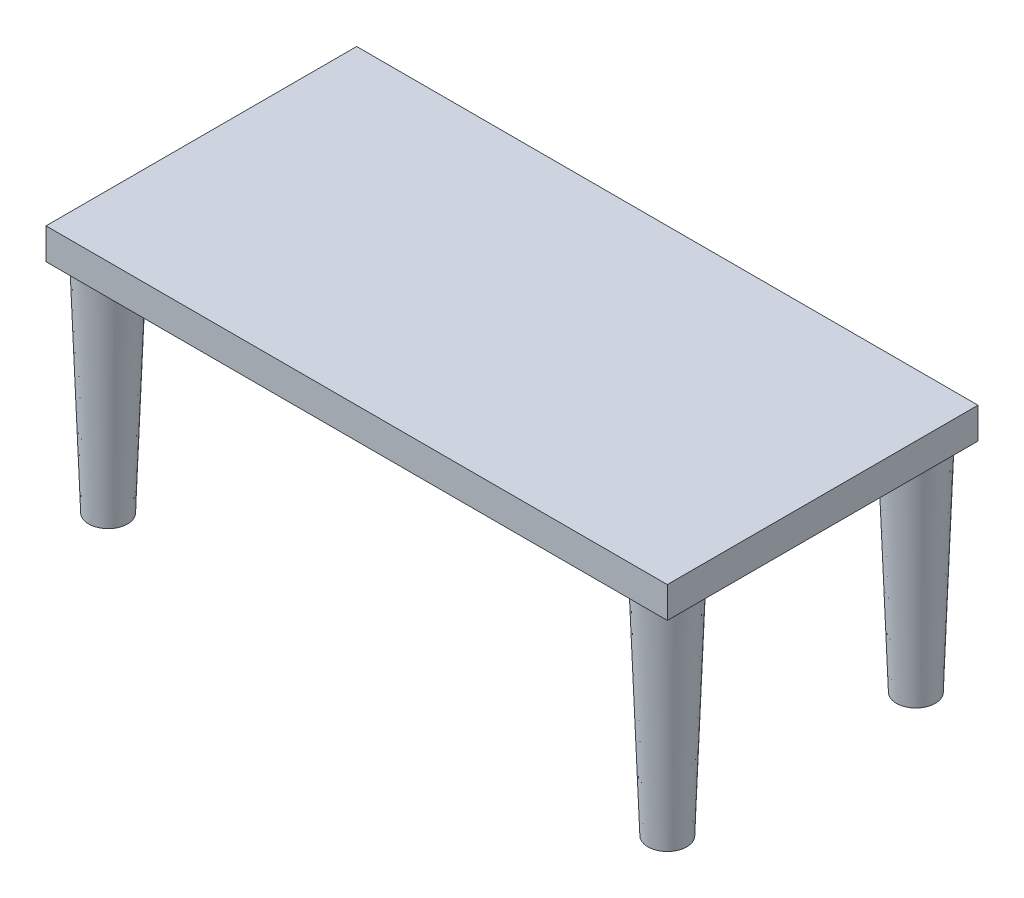
SolidWorks part; units mm, degrees
ref_plane "Front Plane" through (0, 0, 0) normal (0, 0, 1) x (1, 0, 0)
ref_plane "Top Plane" through (0, 0, 0) normal (0, 1, 0) x (1, 0, 0)
ref_plane "Right Plane" through (0, 0, 0) normal (1, 0, 0) x (0, 0, -1)
sketch "Sketch1" plane through (0, 0, 0) normal (0, 1, 0) x (1, 0, 0)
  line L1 (-100, 50) -> (100, 50)
  line L2 (-100, 50) -> (-100, -50)
  line L3 (-100, -50) -> (100, -50)
  line L4 (100, 50) -> (100, -50)
  line L5 (-100, 50) -> (100, -50) construction
  line L6 (-100, -50) -> (100, 50) construction
  point P0 (0, 0)
  dimension "D1" = 100
  dimension "D2" = 200
extrude "Boss-Extrude1" add sketch "Sketch1" along normal mid plane 10
ref_plane "Plane1" through (0, -75, 0) normal (0, 1, 0) x (1, 0, 0)
sketch "Sketch2" plane through (0, -5, 0) normal (0, -1, 0) x (1, 0, 0)
  line L0 (-100, -50) -> (-100, 50) construction
  line L1 (100, -50) -> (-100, -50) construction
  line L2 (100, 50) -> (100, -50) construction
  line L3 (-100, 50) -> (100, 50) construction
  circle A0 centre (-90, 40) radius 8.75
  circle A1 centre (90, 40) radius 8.75
  circle A2 centre (90, -40) radius 8.75
  circle A3 centre (-90, -40) radius 8.75
  dimension "D1" = 17.5
  dimension "D2" = 10
  dimension "D3" = 10
  dimension "D4" = 10
  dimension "D5" = 10
  dimension "D6" = 10
  dimension "D7" = 10
  dimension "D8" = 10
  dimension "D9" = 10
sketch "Sketch3" plane through (0, -75, 0) normal (0, 1, 0) x (1, 0, 0)
  circle A0 centre (-90, -40) radius 6.25
  circle A1 centre (-90, 40) radius 6.25
  circle A2 centre (90, 40) radius 6.25
  circle A3 centre (90, -40) radius 6.25
  dimension "D1" = 12.5
loft "Loft1" add section "Sketch2" section "Sketch3" connector at (-81.3683, -5, -38.5661) connector at (-83.7973, -75, -39.2323)
loft "Loft2" add section "Sketch2<4>" section "Sketch3<3>" connector at (-81.252, -5, 40.1869) connector at (-83.7823, -75, 40.6343)
sketch "Sketch2<4>" plane through (0, -5, 0) normal (0, -1, 0) x (1, 0, 0) same geometry as "Sketch2"
sketch "Sketch3<3>" plane through (0, -75, 0) normal (0, 1, 0) x (1, 0, 0) same geometry as "Sketch3"
loft "Loft3" add section "Sketch2<5>" section "Sketch3<4>" connector at (81.3701, -5, 38.5552) connector at (83.7973, -75, 39.2323)
sketch "Sketch2<5>" plane through (0, -5, 0) normal (0, -1, 0) x (1, 0, 0) same geometry as "Sketch2"
sketch "Sketch3<4>" plane through (0, -75, 0) normal (0, 1, 0) x (1, 0, 0) same geometry as "Sketch3"
loft "Loft4" add section "Sketch2<6>" section "Sketch3<5>" connector at (81.3756, -5, -38.5227) connector at (83.789, -75, -39.3025)
sketch "Sketch2<6>" plane through (0, -5, 0) normal (0, -1, 0) x (1, 0, 0) same geometry as "Sketch2"
sketch "Sketch3<5>" plane through (0, -75, 0) normal (0, 1, 0) x (1, 0, 0) same geometry as "Sketch3"
